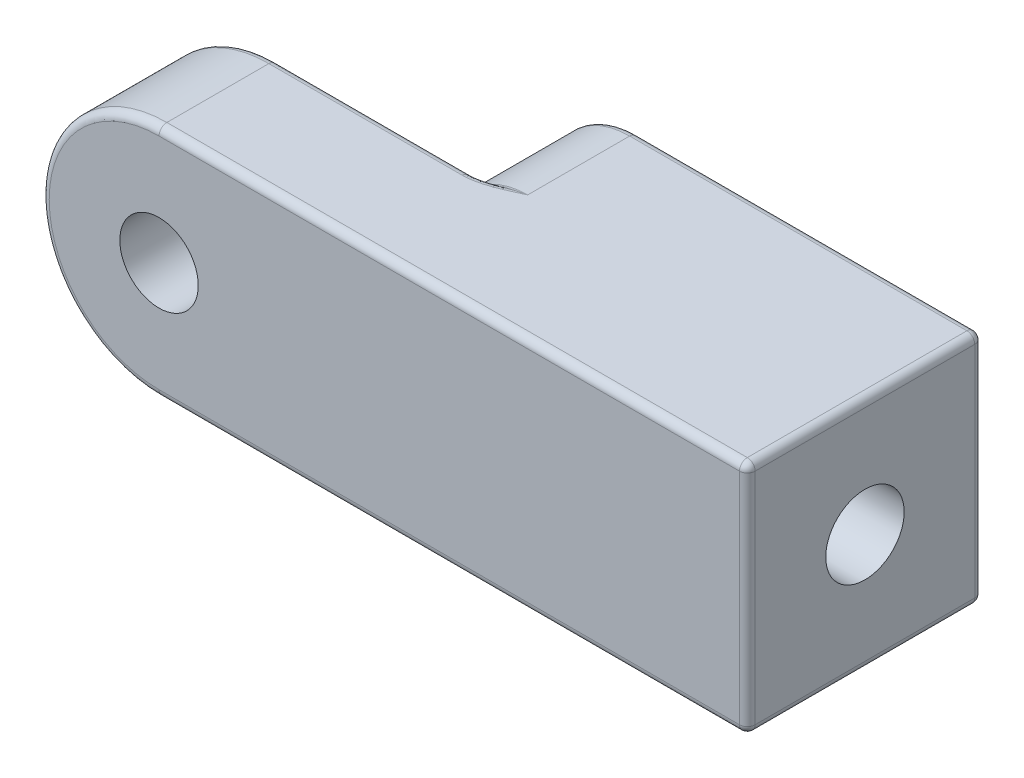
SolidWorks part; units mm, degrees
material "Malleable Cast Iron"
ref_plane "Front Plane" through (0, 0, 0) normal (0, 0, 1) x (1, 0, 0)
ref_plane "Top Plane" through (0, 0, 0) normal (0, 1, 0) x (1, 0, 0)
ref_plane "Right Plane" through (0, 0, 0) normal (1, 0, 0) x (0, 0, -1)
sketch "Sketch1" plane through (0, 0, 0) normal (0, 0, 1) x (1, 0, 0)
  line L0 (0, -30) -> (0, 30)
  line L1 (-150, -30) -> (0, -30)
  line L3 (-150, 30) -> (0, 30)
  arc A0 (-150, 30) -> (-150, -30) centre (-150, 0) ccw
  circle A2 centre (-150, 0) radius 10
  point P0 (0, 0)
  dimension "D1" = 20
  dimension "D2" = 150
  dimension "D3" = 30
extrude "Boss-Extrude1" add sketch "Sketch1" along normal blind 60
sketch "Sketch2" plane through (0, 0, 0) normal (0, 0, 1) x (1, 0, 0)
  line L1 (0, 30) -> (-150, 30) construction
  line L3 (-150, -30) -> (0, -30) construction
  line L8 (-70, 30) -> (-150, 30)
  line L9 (-70, -30) -> (-150, -30)
  line L11 (-70, -30) -> (-108, -30)
  line L13 (-70, 30) -> (-108, 30)
  line L14 (-108, -30) -> (-108, 30)
  arc A1 (-150, 30) -> (-150, -30) centre (-150, 0) ccw
  dimension "D1" = 42
extrude "Cut-Extrude2" cut sketch "Sketch2" along normal blind 30 contours L8 A1 L9 region at (-141.1229, 0, 0)
sketch "Sketch3" plane through (0, 0, 0) normal (1, 0, 0) x (0, 0, -1)
  circle A0 centre (-30, 0) radius 10
  dimension "D1" = 20
  dimension "D2" = 30
extrude "Cut-Extrude3" cut sketch "Sketch3" against normal blind 30
fillet "Fillet1" radius 20 2 edges at (-108, 30, 15) (-108, -30, 15)
fillet "Fillet2" radius 2 18 edges at (-75, -30, 60) (-180, 0, 60) (-119, -30, 30) (-180, 0, 30) (-102.1421, -24.1421, 30) (-102.1421, 24.1421, 30) (0, 0, 0) (-44, 30, 0) (-102.1421, 24.1421, 0) (-108, 0, 0) (-102.1421, -24.1421, 0) (-44, -30, 0) (0, 0, 60) (-75, 30, 60) (0, -30, 30) (0, 30, 30) (-119, 30, 30) (-108, 0, 30)
